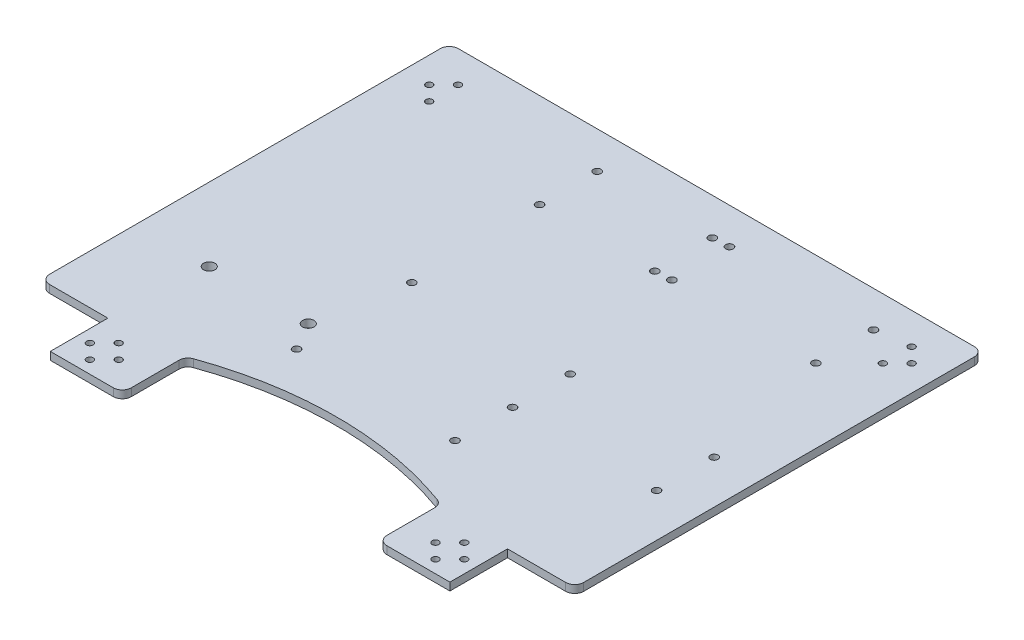
SolidWorks part; units mm, degrees
material "Acrylic (Medium-high impact)"
ref_plane "Front" through (0, 0, 0) normal (0, 0, 1) x (1, 0, 0)
ref_plane "Top" through (0, 0, 0) normal (0, 1, 0) x (1, 0, 0)
ref_plane "Right" through (0, 0, 0) normal (1, 0, 0) x (0, 0, -1)
ref_axis "side-side" through (80.9, 0, 0) along (-1, 0, 0)
ref_axis "up-down" through (0, 50, 0) along (0, -1, 0)
ref_axis "front-back" through (0, 0, -80.9) along (0, 0, 1)
sketch "Sketch1" plane through (0, 0, 0) normal (0, 1, 0) x (1, 0, 0)
  line L0 (-148.318, 44.044) -> (-144, 44.044) construction
  line L1 (-148.318, -215.956) -> (-148.318, 44.044) construction
  line L2 (-143.318, 44.044) -> (143.318, 44.044)
  line L3 (-148.318, -177.956) -> (-148.318, 39.044)
  line L4 (-141.5, -183.956) -> (-114.5, -183.956) construction
  line L5 (-112, -186.456) -> (-112, -213.456) construction
  line L6 (-47.6822, -65.9555) -> (-47.6822, -160.956) construction
  line L7 (-42.6822, -165.956) -> (-36.1822, -165.956) construction
  line L8 (-143.318, -182.956) -> (-111, -182.956)
  line L9 (-111, -214.956) -> (-111, -182.956)
  line L11 (111, -214.956) -> (111, -182.956)
  line L12 (111, -182.956) -> (143.318, -182.956)
  line L14 (-76, -214.956) -> (-111, -214.956)
  line L15 (-71, -209.956) -> (-71, -183.4381)
  line L16 (71, -183.4381) -> (71, -209.956)
  line L17 (76, -214.956) -> (111, -214.956)
  line L18 (-144, -215.956) -> (144, -215.956) construction
  line L19 (112, -213.456) -> (112, -186.456) construction
  line L20 (148.318, 44.044) -> (148.318, -215.956) construction
  line L21 (148.318, 39.044) -> (148.318, -177.956)
  line L22 (112, -183.956) -> (114, -183.956) construction
  arc A0 (-67.6923, -178.7332) -> (67.6923, -178.7332) centre (0, -366.9293) cw
  arc A1 (71, -209.956) -> (76, -214.956) centre (76, -209.956) ccw
  arc A2 (-71, -209.956) -> (-76, -214.956) centre (-76, -209.956) cw
  arc A3 (-71, -183.4381) -> (-67.6923, -178.7332) centre (-66, -183.4381) cw
  arc A4 (67.6923, -178.7332) -> (71, -183.4381) centre (66, -183.4381) cw
  arc A5 (143.318, -182.956) -> (148.318, -177.956) centre (143.318, -177.956) ccw
  arc A6 (148.318, 39.044) -> (143.318, 44.044) centre (143.318, 39.044) ccw
  arc A7 (-143.318, 44.044) -> (-148.318, 39.044) centre (-143.318, 39.044) ccw
  arc A8 (-143.318, -182.956) -> (-148.318, -177.956) centre (-143.318, -177.956) cw
  circle A9 centre (126, 26.544) radius 1.85 construction
  circle A10 centre (134, 18.544) radius 1.85 construction
  circle A11 centre (126, 10.544) radius 1.85 construction
  circle A12 centre (126, 26.544) radius 1.85
  circle A13 centre (134, 18.544) radius 1.85
  circle A14 centre (126, 10.544) radius 1.85
  circle A15 centre (107.318, -7.956) radius 2.1 construction
  circle A16 centre (107.318, 24.044) radius 2.1 construction
  circle A17 centre (107.318, -7.956) radius 2.1
  circle A18 centre (107.318, 24.044) radius 2.1
  circle A19 centre (18.318, 23.544) radius 2.1 construction
  circle A20 centre (27.318, 24.044) radius 2.1 construction
  circle A21 centre (18.318, -8.456) radius 2.1 construction
  circle A22 centre (27.318, -7.956) radius 2.1 construction
  circle A23 centre (18.318, 23.544) radius 2.1
  circle A24 centre (27.318, 24.044) radius 2.1
  circle A25 centre (18.318, -8.456) radius 2.1
  circle A26 centre (27.318, -7.956) radius 2.1
  circle A27 centre (-134, 18.544) radius 1.85 construction
  circle A28 centre (-126, 10.544) radius 1.85 construction
  circle A29 centre (-126, 26.544) radius 1.85 construction
  circle A30 centre (-45.682, -8.456) radius 2.1 construction
  circle A31 centre (-45.682, 23.544) radius 2.1 construction
  circle A32 centre (-134, 18.544) radius 1.85
  circle A33 centre (-126, 10.544) radius 1.85
  circle A34 centre (-126, 26.544) radius 1.85
  circle A35 centre (-45.682, -8.456) radius 2.1
  circle A36 centre (-45.682, 23.544) radius 2.1
  circle A37 centre (-43.6822, -145.456) radius 2.1 construction
  circle A38 centre (-43.6822, -81.4555) radius 2.1 construction
  circle A39 centre (-43.6822, -145.456) radius 2.1
  circle A40 centre (-43.6822, -81.4555) radius 2.1
  circle A41 centre (44.318, -145.456) radius 2.1 construction
  circle A42 centre (44.318, -113.456) radius 2.1 construction
  circle A43 centre (44.318, -81.4555) radius 2.1 construction
  circle A44 centre (44.318, -145.456) radius 2.1
  circle A45 centre (44.318, -113.456) radius 2.1
  circle A46 centre (44.318, -81.4555) radius 2.1
  circle A47 centre (-96, -191.956) radius 1.85 construction
  circle A48 centre (-104, -199.956) radius 1.85 construction
  circle A49 centre (-88, -199.956) radius 1.85 construction
  circle A50 centre (-96, -191.956) radius 1.85
  circle A51 centre (-104, -199.956) radius 1.85
  circle A52 centre (-88, -199.956) radius 1.85
  circle A53 centre (-96, -207.956) radius 1.85 construction
  circle A54 centre (-96, -207.956) radius 1.85
  circle A55 centre (96, -207.956) radius 1.85 construction
  circle A56 centre (96, -207.956) radius 1.85
  circle A57 centre (96, -191.956) radius 1.85 construction
  circle A58 centre (96, -191.956) radius 1.85
  circle A59 centre (104, -199.956) radius 1.85 construction
  circle A60 centre (104, -199.956) radius 1.85
  circle A61 centre (88, -199.956) radius 1.85 construction
  circle A62 centre (88, -199.956) radius 1.85
  circle A63 centre (124.318, -81.4555) radius 2.1 construction
  circle A64 centre (124.318, -81.4555) radius 2.1
  circle A65 centre (124.318, -113.4555) radius 2.1 construction
  circle A66 centre (124.318, -113.4555) radius 2.1
  circle A67 centre (-52.6822, -129.956) radius 3.175
  circle A68 centre (-107.6822, -129.956) radius 3.175
  point P33 (-71, -179.956)
  point P36 (71, -179.956)
  dimension "D9" = 200
  dimension "D10" = 5
  dimension "D11" = 6.35
  dimension "D1" = 1
  dimension "D2" = 1
  dimension "D3" = 1
  dimension "D4" = 1
  dimension "D5" = 1
  dimension "D6" = 40
  dimension "D7" = 40
  dimension "D8" = 35
  dimension "D12" = 55
  dimension "D13" = 5
  dimension "D14" = 36
extrude "Boss-Extrude1" add sketch "Sketch1" along normal blind 4.3
